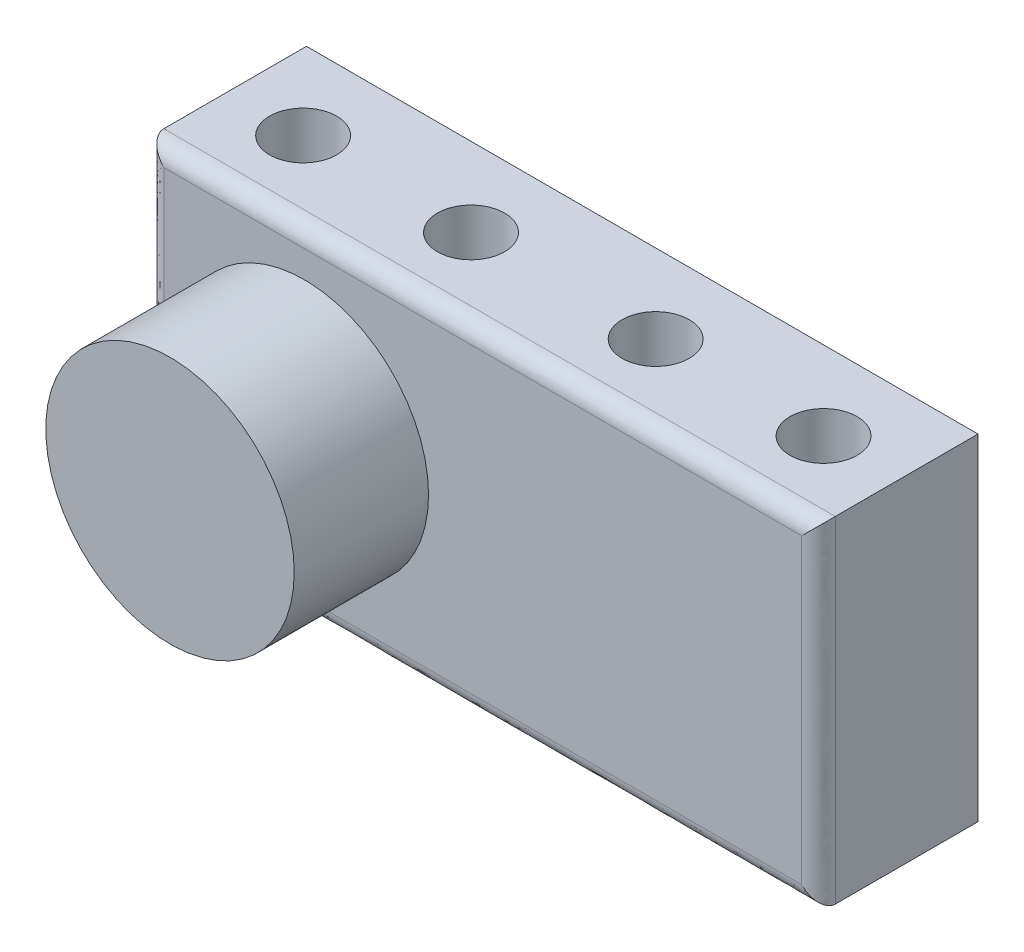
SolidWorks part; units mm, degrees
material "petg 20%"
ref_plane "Front Plane" through (0, 0, 0) normal (0, 0, 1) x (1, 0, 0)
ref_plane "Top Plane" through (0, 0, 0) normal (0, 1, 0) x (1, 0, 0)
ref_plane "Right Plane" through (0, 0, 0) normal (1, 0, 0) x (0, 0, -1)
sketch "Sketch1" plane through (0, 0, 0) normal (0, 0, 1) x (1, 0, 0)
  line L1 (-20, 10) -> (20, 10)
  line L2 (-20, 10) -> (-20, -10)
  line L3 (-20, -10) -> (20, -10)
  line L4 (20, 10) -> (20, -10)
  line L5 (-20, 10) -> (20, -10) construction
  line L6 (-20, -10) -> (20, 10) construction
  point P0 (0, 0)
  dimension "D1" = 40
  dimension "D2" = 20
extrude "Boss-Extrude1" add sketch "Sketch1" along normal blind 9.5
fillet "Fillet1" radius 1 4 edges at (0, -10, 9.5) (20, 0, 9.5) (0, 10, 9.5) (-20, 0, 9.5) first distance on face at (0, -10, 4.75) first distance on face at (20, 0, 4.75) first distance on face at (0, 10, 4.75) first distance on face at (-20, 0, 4.75)
sketch "Sketch4" plane through (0, 0, 9.5) normal (0, 0, 1) x (1, 0, 0)
  circle A0 centre (-10.6286, 0) radius 7.4
  dimension "D1" = 14.8
extrude "Boss-Extrude2" add sketch "Sketch4" along normal blind 8
sketch "Sketch5" plane through (0, -10, 0) normal (0, -1, 0) x (1, 0, 0)
  circle A0 centre (-15.5, 4.7) radius 2
  circle A1 centre (-5.5, 4.7) radius 2
  circle A2 centre (5.5, 4.7) radius 2
  circle A3 centre (15.5, 4.7) radius 2
extrude "Cut-Extrude1" cut sketch "Sketch5" against normal through all
